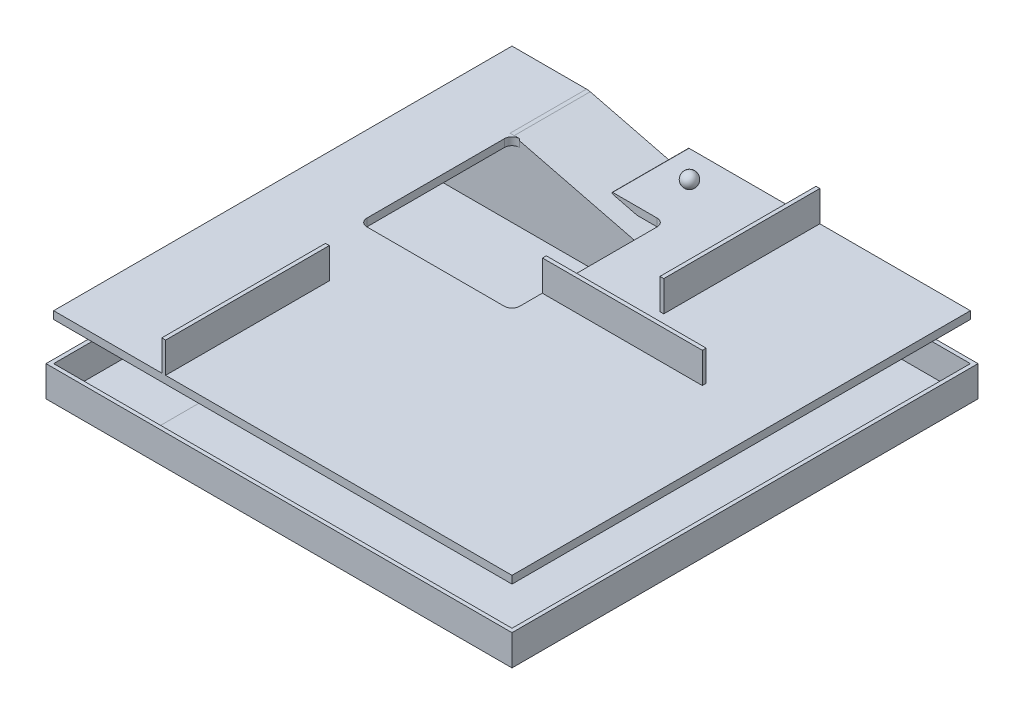
SolidWorks part; units mm, degrees
ref_plane "前视基准面" through (0, 0, 0) normal (0, 0, 1) x (1, 0, 0)
ref_plane "上视基准面" through (0, 0, 0) normal (0, 1, 0) x (1, 0, 0)
ref_plane "右视基准面" through (0, 0, 0) normal (1, 0, 0) x (0, 0, -1)
other "Configuration Table"
sketch "草图1" plane through (0, 0, 0) normal (0, 1, 0) x (1, 0, 0)
  line L0 (-50, -50) -> (-50, 6050)
  line L1 (0, 0) -> (6000, 0)
  line L2 (0, 0) -> (0, 6000)
  line L3 (0, 6000) -> (6000, 6000)
  line L4 (6000, 0) -> (6000, 6000)
  line L5 (-50, 6050) -> (6050, 6050)
  line L6 (6050, -50) -> (6050, 6050)
  line L7 (-50, -50) -> (6050, -50)
  dimension "D1" = 6000
  dimension "D2" = 6000
  dimension "D3" = 50
extrude "凸台-拉伸1" add sketch "草图1" along normal blind 400
sketch "草图2" plane through (0, 0, 0) normal (0, 1, 0) x (1, 0, 0)
  line L0 (0, 6000) -> (0, 0) construction
  line L1 (0, 0) -> (6000, 0) construction
  line L2 (6000, 0) -> (6000, 6000) construction
  line L3 (6000, 6000) -> (0, 6000) construction
  line L4 (1000, 0) -> (6000, 0)
  line L5 (6000, 0) -> (6000, 6000)
  line L6 (6000, 6000) -> (0, 6000)
  line L7 (0, 6000) -> (0, 1000)
  line L11 (0, 1000) -> (1000, 1000)
  line L12 (1000, 0) -> (1000, 1000)
  dimension "D1" = 1000
  dimension "D2" = 1000
surface "曲面-基准面2" sketch "草图2"
sketch "草图3" plane through (0, 0, 0) normal (0, 1, 0) x (1, 0, 0)
  line L1 (0, 0) -> (1000, 0)
  line L2 (0, 0) -> (0, 1000)
  line L3 (0, 1000) -> (1000, 1000)
  line L4 (1000, 0) -> (1000, 1000)
  dimension "D1" = 1000
  dimension "D2" = 1000
surface "曲面-基准面3" sketch "草图3"
sketch "草图5" plane through (0, 0, -6000) normal (0, 0, 1) x (1, 0, 0)
  line L0 (6000, 400) -> (6000, 0) construction
  line L1 (5000, 0) -> (1000, 1000)
  line L2 (1000, 1000) -> (0, 1000)
  line L3 (0, 1000) -> (0, 0)
  line L4 (0, 0) -> (5000, 0)
  dimension "D1" = 1000
  dimension "D2" = 1000
  dimension "D3" = 1000
  dimension "D4" = 14.036
extrude "凸台-拉伸2" add sketch "草图5" along normal blind 1000
sketch "草图6" plane through (0, 1000, 0) normal (0, 1, 0) x (1, 0, 0)
  line L1 (0, 0) -> (6000, 0)
  line L2 (0, 0) -> (0, 6000)
  line L3 (0, 6000) -> (6000, 6000)
  line L4 (6000, 0) -> (6000, 6000)
  line L5 (1100, 5000) -> (2900, 5000)
  line L6 (1000, 4900) -> (1000, 3100)
  line L7 (1100, 3000) -> (2900, 3000)
  line L8 (3000, 4900) -> (3000, 3100)
  arc A0 (2900, 3000) -> (3000, 3100) centre (2900, 3100) ccw
  arc A1 (2900, 5000) -> (3000, 4900) centre (2900, 4900) cw
  arc A2 (1000, 3100) -> (1100, 3000) centre (1100, 3100) ccw
  arc A3 (1100, 5000) -> (1000, 4900) centre (1100, 4900) ccw
  point P12 (3000, 3000)
  point P15 (3000, 5000)
  point P20 (1000, 5000)
  dimension "D3" = 100
  dimension "D4" = 100
  dimension "D5" = 100
  dimension "D6" = 100
  dimension "D1" = 2000
  dimension "D2" = 2000
  dimension "D7" = 1000
  dimension "D8" = 1000
extrude "凸台-拉伸3" add sketch "草图6" against normal blind 100
sketch "草图9" plane through (294.1176, 1176.4706, 0) normal (0.2425, 0.9701, 0) x (0.9701, -0.2425, 0)
  line L0 (-97.0143, 5000) -> (-97.0143, 6000)
  line L1 (-97.0143, 6000) -> (-97.0143, 5000) construction
  line L5 (3201.4703, 6000) -> (1139.9174, 6000)
  line L6 (1139.9174, 6000) -> (1139.9174, 5000)
  line L7 (1139.9174, 5000) -> (4850.7125, 5000)
  line L8 (4850.7125, 5000) -> (4850.7125, 6000)
  line L9 (4850.7125, 6000) -> (3201.4703, 6000)
  line L10 (3201.4703, 6000) -> (-97.0143, 6000)
  line L11 (1139.9174, 6000) -> (1139.9174, 5000) construction
  line L12 (-97.0143, 5000) -> (4850.7125, 5000)
  line L13 (4850.7125, 5000) -> (4850.7125, 6000)
  line L14 (4850.7125, 6000) -> (3201.4703, 6000)
  point P10 (-97.0143, 5500)
  dimension "D1" = 0
extrude "切除-拉伸1" cut sketch "草图9" along normal blind 300
fillet "圆角1" radius 10 1 edges at (2236.9317, 1000, -5500)
fillet "圆角2" radius 200 1 edges at (1000, 1000, -5500)
sketch "草图10" plane through (0, 1000, 0) normal (0, 1, 0) x (1, 0, 0)
  line L0 (1000, 0) -> (6000, 0) construction
  line L1 (1415.8764, 0) -> (1465.8764, 0)
  line L2 (1415.8764, 0) -> (1415.8764, 2142.7422)
  line L3 (1415.8764, 2142.7422) -> (1465.8764, 2142.7422)
  line L4 (1465.8764, 0) -> (1465.8764, 2142.7422)
  line L5 (6000, 6000) -> (3400, 6000) construction
  line L6 (3002.7743, 3446.7245) -> (5094.5943, 3446.7245)
  line L7 (3002.7743, 3446.7245) -> (3002.7743, 3396.7245)
  line L8 (3002.7743, 3396.7245) -> (5094.5943, 3396.7245)
  line L9 (5094.5943, 3446.7245) -> (5094.5943, 3396.7245)
  line L10 (4029.3269, 6000) -> (3979.3269, 6000)
  line L11 (4029.3269, 6000) -> (4029.3269, 3957.1325)
  line L12 (4029.3269, 3957.1325) -> (3979.3269, 3957.1325)
  line L13 (3979.3269, 6000) -> (3979.3269, 3957.1325)
  dimension "D1" = 50
  dimension "D2" = 50
  dimension "D3" = 50
extrude "凸台-拉伸4" add sketch "草图10" along normal blind 400
ref_plane "基准面1" through (0, 1095, 0) normal (0, 1, 0) x (1, 0, 0)
sketch "草图12" plane through (0, 1095, 0) normal (0, 1, 0) x (1, 0, 0)
  line L0 (2768.8692, 4554.4454) -> (2768.8692, 54554.4454) construction
  circle A0 centre (2768.8692, 5554.4454) radius 95
revolve "旋转2" add sketch "草图12" angle 360 about L0
